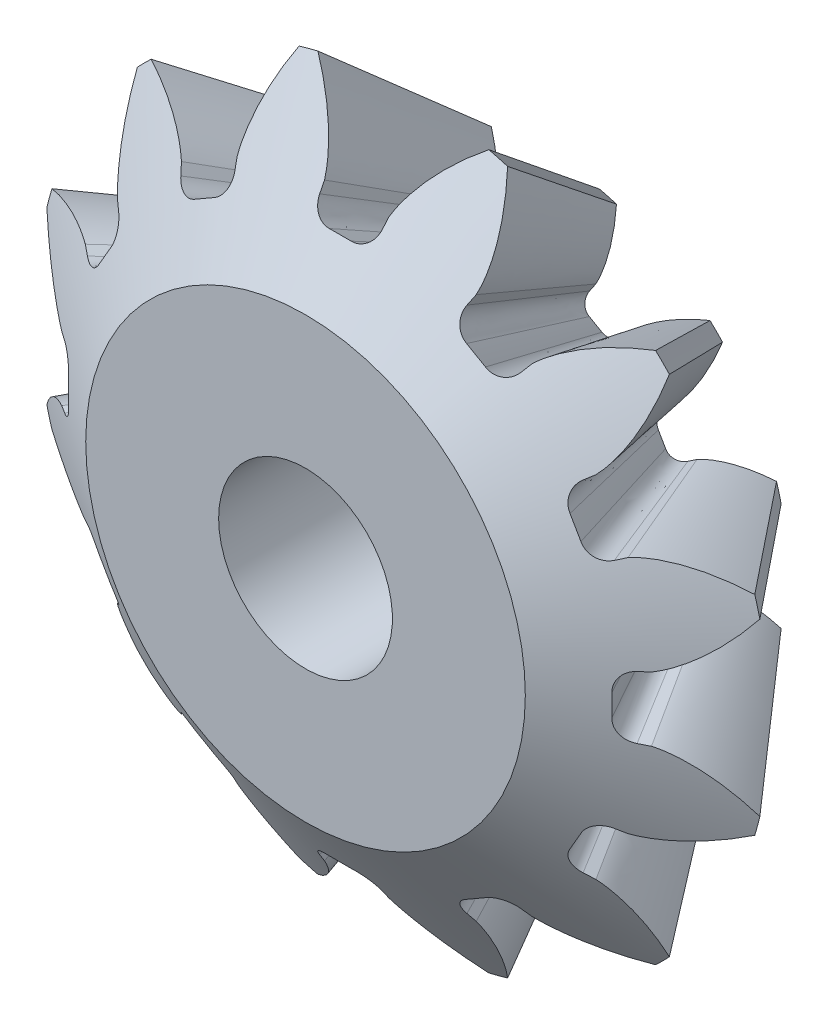
SolidWorks part; units mm, degrees
ref_plane "Front Plane" through (0, 0, 0) normal (0, 0, 1) x (1, 0, 0)
ref_plane "Top Plane" through (0, 0, 0) normal (0, 1, 0) x (1, 0, 0)
ref_plane "Right Plane" through (0, 0, 0) normal (1, 0, 0) x (0, 0, -1)
ref_axis "Gear Axis" through (0, 0, -1.3521) along (0, 0, 1)
sketch "Blank Sketch" plane through (0, 0, 0) normal (0, 1, 0) x (1, 0, 0)
  line L0 (0, 0) -> (0, -27.0416) construction
  line L1 (0, 0) -> (15, -22.5) construction
  line L2 (0, 0) -> (10.0077, -15.0115) construction
  line L3 (6.2136, -17.5409) -> (11.62, -13.9367)
  line L4 (11.62, -13.9367) -> (17.6117, -20.7589)
  line L5 (17.6117, -20.7589) -> (10.5604, -25.4597)
  line L6 (10.5604, -25.4597) -> (4.175, -25.4597)
  line L7 (4.175, -25.4597) -> (4.175, -17.5409)
  line L8 (4.175, -17.5409) -> (6.2136, -17.5409)
  line L9 (15, -22.5) -> (17.6117, -20.7589) construction
  line L10 (15, -22.5) -> (10.5604, -25.4597) construction
  line L11 (10.0077, -15.0115) -> (6.2136, -17.5409) construction
  dimension "Axis" = 27.0416
  dimension "Cone" = 33.69
  dimension "Heel" = 27.0416
  dimension "Toe Cone" = 33.69
  dimension "Toe" = 18.0416
  dimension "Heel Square" = 90
  dimension "Addendum" = 3.1389
  dimension "Root Square" = 90
  dimension "Heel Rim" = 5.3357
  dimension "Toe Square" = 90
  dimension "Toe Rim" = 4.5599
  dimension "Front Square" = 90
  dimension "Face" = 7.602
  dimension "Back" = 6.3854
  dimension "Front" = 2.0386
revolve "Blank" add sketch "Blank Sketch" angle 360 about L0
sketch "Cone Sketch" plane through (0, 0, 0) normal (0, 1, 0) x (1, 0, 0)
  line L0 (0, 0) -> (0, -27.0416) construction
  line L1 (0, 0) -> (16.3868, -24.5801)
  line L2 (0, 0) -> (8.6209, -12.9314)
  dimension "Axis" = 27.0416
  dimension "Toe Cone" = 33.69
  dimension "Heel Cone" = 33.69
  dimension "Heel" = 29.5416
  dimension "Toe" = 15.5416
ref_plane "Heel Plane" through (16.3868, 0, 24.5801) normal (0.5547, 0, 0.8321) x (0.8321, 0, -0.5547)
ref_plane "Toe Plane" through (8.6209, 0, 12.9314) normal (0.5547, 0, 0.8321) x (0.8321, 0, -0.5547)
sketch "Heel Section Sketch" plane through (16.3868, 0, 24.5801) normal (0.5547, 0, 0.8321) x (0.8321, 0, -0.5547)
  line L0 (0, 0) -> (-19.6944, 0) construction
  line L1 (-1.0664, 1.6899) -> (-1.6127, 1.6403)
  line L2 (-1.0664, -1.6899) -> (-1.6127, -1.6403)
  line L3 (5.066, 7.4419) -> (5.066, -7.4419)
  arc A0 (-1.6127, 1.6403) -> (-2.5562, 0.5721) centre (-1.5189, 0.6067) ccw
  arc A1 (-2.5562, -0.5721) -> (-1.6127, -1.6403) centre (-1.5189, -0.6067) ccw
  arc A2 (-2.5562, -0.5721) -> (-2.5562, 0.5721) centre (-19.6944, 0) ccw
  spline S0 degree 4 poles (-1.2286, 1.6567) (-1.181, 1.6651) (-1.0984, 1.6813) (-1.0131, 1.7021) (-0.8228, 1.7564) (-0.6581, 1.8142) (-0.4389, 1.8979) (-0.2207, 1.9951) (0.0234, 2.1136) (0.2563, 2.2395) (0.4886, 2.3742) (0.7144, 2.5158) (0.956, 2.6769) (1.2463, 2.8844) (1.5815, 3.1433) (1.9563, 3.4606) (2.3479, 3.8229) (2.7249, 4.2038) (3.0844, 4.5958) (3.432, 5.0072) (3.759, 5.4208) (4.0808, 5.8628) (4.3344, 6.231) (4.5664, 6.5952) (4.7511, 6.8911) (4.9903, 7.3038) (5.1238, 7.5431) (5.3385, 7.948) (5.41, 8.0942) (5.4674, 8.2082) knots 0 0 0 0 0 0.016753 0.031571 0.050064 0.068907 0.096646 0.124386 0.152126 0.179865 0.207605 0.235344 0.263084 0.300343 0.355823 0.411302 0.466781 0.52226 0.577739 0.633218 0.688697 0.744176 0.799656 0.827395 0.855135 0.910614 0.955307 1 1 1 1 1 construction
  spline S1 degree 4 poles (-1.0664, 1.6899) (-1.0354, 1.6973) (-0.9668, 1.7153) (-0.8228, 1.7564) (-0.6581, 1.8142) (-0.4389, 1.8979) (-0.2207, 1.9951) (0.0234, 2.1136) (0.2563, 2.2395) (0.4886, 2.3742) (0.7144, 2.5158) (0.956, 2.6769) (1.2463, 2.8844) (1.5815, 3.1433) (1.9563, 3.4606) (2.3479, 3.8229) (2.7249, 4.2038) (3.0844, 4.5958) (3.432, 5.0072) (3.759, 5.4208) (4.0808, 5.8628) (4.3344, 6.231) (4.5664, 6.5952) (4.7511, 6.8911) (4.9216, 7.1853) (5.0082, 7.3375) (5.066, 7.4419) knots 0.016753 0.016753 0.016753 0.016753 0.016753 0.031571 0.050064 0.068907 0.096646 0.124386 0.152126 0.179865 0.207605 0.235344 0.263084 0.300343 0.355823 0.411302 0.466781 0.52226 0.577739 0.633218 0.688697 0.744176 0.799656 0.827395 0.855135 0.910614 0.910614 0.910614 0.910614 0.910614
  spline S2 degree 4 poles (-1.2286, -1.6567) (-1.181, -1.6651) (-1.0984, -1.6813) (-1.0131, -1.7021) (-0.8228, -1.7564) (-0.6581, -1.8142) (-0.4389, -1.8979) (-0.2207, -1.9951) (0.0234, -2.1136) (0.2563, -2.2395) (0.4886, -2.3742) (0.7144, -2.5158) (0.956, -2.6769) (1.2463, -2.8844) (1.5815, -3.1433) (1.9563, -3.4606) (2.3479, -3.8229) (2.7249, -4.2038) (3.0844, -4.5958) (3.432, -5.0072) (3.759, -5.4208) (4.0808, -5.8628) (4.3344, -6.231) (4.5664, -6.5952) (4.7511, -6.8911) (4.9903, -7.3038) (5.1238, -7.5431) (5.3385, -7.948) (5.41, -8.0942) (5.4674, -8.2082) knots 0 0 0 0 0 0.016753 0.031571 0.050064 0.068907 0.096646 0.124386 0.152126 0.179865 0.207605 0.235344 0.263084 0.300343 0.355823 0.411302 0.466781 0.52226 0.577739 0.633218 0.688697 0.744176 0.799656 0.827395 0.855135 0.910614 0.955307 1 1 1 1 1 construction
  spline S3 degree 4 poles (-1.0664, -1.6899) (-1.0354, -1.6973) (-0.9668, -1.7153) (-0.8228, -1.7564) (-0.6581, -1.8142) (-0.4389, -1.8979) (-0.2207, -1.9951) (0.0234, -2.1136) (0.2563, -2.2395) (0.4886, -2.3742) (0.7144, -2.5158) (0.956, -2.6769) (1.2463, -2.8844) (1.5815, -3.1433) (1.9563, -3.4606) (2.3479, -3.8229) (2.7249, -4.2038) (3.0844, -4.5958) (3.432, -5.0072) (3.759, -5.4208) (4.0808, -5.8628) (4.3344, -6.231) (4.5664, -6.5952) (4.7511, -6.8911) (4.9216, -7.1853) (5.0082, -7.3375) (5.066, -7.4419) knots 0.016753 0.016753 0.016753 0.016753 0.016753 0.031571 0.050064 0.068907 0.096646 0.124386 0.152126 0.179865 0.207605 0.235344 0.263084 0.300343 0.355823 0.411302 0.466781 0.52226 0.577739 0.633218 0.688697 0.744176 0.799656 0.827395 0.855135 0.910614 0.910614 0.910614 0.910614 0.910614
  dimension "Root" = 17.1478
  dimension "Fillet" = 1.0378
  dimension "Centre" = 19.6944
sketch "Toe Section Sketch" plane through (8.6209, 0, 12.9314) normal (0.5547, 0, 0.8321) x (0.8321, 0, -0.5547)
  line L0 (0, 0) -> (-10.3611, 0) construction
  line L1 (-0.561, 0.889) -> (-0.8484, 0.863)
  line L2 (-0.561, -0.889) -> (-0.8484, -0.863)
  line L3 (2.6652, 3.9151) -> (2.6652, -3.9151)
  arc A0 (-0.8484, 0.863) -> (-1.3448, 0.301) centre (-0.7991, 0.3192) ccw
  arc A1 (-1.3448, -0.301) -> (-0.8484, -0.863) centre (-0.7991, -0.3192) ccw
  arc A2 (-1.3448, -0.301) -> (-1.3448, 0.301) centre (-10.3611, 0) ccw
  spline S0 degree 4 poles (-0.6464, 0.8716) (-0.6213, 0.876) (-0.5778, 0.8845) (-0.533, 0.8955) (-0.4329, 0.924) (-0.3462, 0.9544) (-0.2309, 0.9985) (-0.1161, 1.0496) (0.0123, 1.112) (0.1348, 1.1782) (0.2571, 1.2491) (0.3758, 1.3235) (0.503, 1.4084) (0.6555, 1.5172) (0.8323, 1.6541) (1.0288, 1.8199) (1.2358, 2.0122) (1.4327, 2.21) (1.6242, 2.4204) (1.8032, 2.6299) (1.9816, 2.859) (2.1402, 3.0723) (2.311, 3.3268) (2.4415, 3.5271) (2.6102, 3.8151) (2.6985, 3.9736) (2.8046, 4.1741) (2.849, 4.2635) (2.8753, 4.3163) knots 0 0 0 0 0 0.016753 0.031571 0.050064 0.068907 0.096646 0.124386 0.152126 0.179865 0.207605 0.235344 0.263084 0.300343 0.355823 0.411302 0.466781 0.52226 0.577739 0.633218 0.688697 0.744176 0.799656 0.855135 0.910614 0.955307 1 1 1 1 1 construction
  spline S1 degree 4 poles (-0.561, 0.889) (-0.5447, 0.893) (-0.5086, 0.9024) (-0.4329, 0.924) (-0.3462, 0.9544) (-0.2309, 0.9985) (-0.1161, 1.0496) (0.0123, 1.112) (0.1348, 1.1782) (0.2571, 1.2491) (0.3758, 1.3235) (0.503, 1.4084) (0.6555, 1.5172) (0.8323, 1.6541) (1.0288, 1.8199) (1.2358, 2.0122) (1.4327, 2.21) (1.6242, 2.4204) (1.8032, 2.6299) (1.9816, 2.859) (2.1402, 3.0723) (2.311, 3.3268) (2.4415, 3.5271) (2.5745, 3.7541) (2.6348, 3.8602) (2.6652, 3.9151) knots 0.016753 0.016753 0.016753 0.016753 0.016753 0.031571 0.050064 0.068907 0.096646 0.124386 0.152126 0.179865 0.207605 0.235344 0.263084 0.300343 0.355823 0.411302 0.466781 0.52226 0.577739 0.633218 0.688697 0.744176 0.799656 0.855135 0.910614 0.910614 0.910614 0.910614 0.910614
  spline S2 degree 4 poles (-0.6464, -0.8716) (-0.6213, -0.876) (-0.5778, -0.8845) (-0.533, -0.8955) (-0.4329, -0.924) (-0.3462, -0.9544) (-0.2309, -0.9985) (-0.1161, -1.0496) (0.0123, -1.112) (0.1348, -1.1782) (0.2571, -1.2491) (0.3758, -1.3235) (0.503, -1.4084) (0.6555, -1.5172) (0.8323, -1.6541) (1.0288, -1.8199) (1.2358, -2.0122) (1.4327, -2.21) (1.6242, -2.4204) (1.8032, -2.6299) (1.9816, -2.859) (2.1402, -3.0723) (2.311, -3.3268) (2.4415, -3.5271) (2.6102, -3.8151) (2.6985, -3.9736) (2.8046, -4.1741) (2.849, -4.2635) (2.8753, -4.3163) knots 0 0 0 0 0 0.016753 0.031571 0.050064 0.068907 0.096646 0.124386 0.152126 0.179865 0.207605 0.235344 0.263084 0.300343 0.355823 0.411302 0.466781 0.52226 0.577739 0.633218 0.688697 0.744176 0.799656 0.855135 0.910614 0.955307 1 1 1 1 1 construction
  spline S3 degree 4 poles (-0.561, -0.889) (-0.5447, -0.893) (-0.5086, -0.9024) (-0.4329, -0.924) (-0.3462, -0.9544) (-0.2309, -0.9985) (-0.1161, -1.0496) (0.0123, -1.112) (0.1348, -1.1782) (0.2571, -1.2491) (0.3758, -1.3235) (0.503, -1.4084) (0.6555, -1.5172) (0.8323, -1.6541) (1.0288, -1.8199) (1.2358, -2.0122) (1.4327, -2.21) (1.6242, -2.4204) (1.8032, -2.6299) (1.9816, -2.859) (2.1402, -3.0723) (2.311, -3.3268) (2.4415, -3.5271) (2.5745, -3.7541) (2.6348, -3.8602) (2.6652, -3.9151) knots 0.016753 0.016753 0.016753 0.016753 0.016753 0.031571 0.050064 0.068907 0.096646 0.124386 0.152126 0.179865 0.207605 0.235344 0.263084 0.300343 0.355823 0.411302 0.466781 0.52226 0.577739 0.633218 0.688697 0.744176 0.799656 0.855135 0.910614 0.910614 0.910614 0.910614 0.910614
  dimension "Root" = 9.0213
  dimension "Fillet" = 0.546
  dimension "Centre" = 10.3611
loft "Tooth Space" cut profiles "Heel Section Sketch", "Toe Section Sketch"
pattern_circular "Teeth" count 12 over 360 about axis through (0, 0, -1.3521) along (0, 0, 1) of "Tooth Space"
equation "\"No. of Teeth\"= 12"
equation "\"Module\"= 2.5"
equation "\"Bore Diameter\"= 8.35"
equation "\"Pressure Angle\"= 20"
equation "\"Shaft Angle\"= 90"
equation "\"Mate Teeth\"= 18"
equation "\"Pitch Cone Angle\"= IIF ( ( \"Mate Teeth\" / \"No. of Teeth\" + cos ( \"Shaft Angle\" ) ) > 0 , atn ( sin ( \"Shaft Angle\" ) / ( \"Mate Teeth\" / \"No. of Teeth\" + cos ( \"Shaft Angle\" ) ) ) , 180 + atn ( sin ( \"Shaft Angle\" ) / ( \"Mate Teeth\" / \"No. of Teeth\" + cos ( \"Shaft Angle\" ) ) ) )"
equation "\"Mate Cone Angle\"= \"Shaft Angle\" - \"Pitch Cone Angle\""
equation "\"Addendum\"= IIF ( \"No. of Teeth\" >= \"Mate Teeth\" , 0.54 * \"Module\" + 0.46 * \"Module\" / ( ( \"No. of Teeth\" * cos ( \"Mate Cone Angle\" ) ) / ( \"Mate Teeth\" * cos ( \"Pitch Cone Angle\" ) ) ) , 2 * \"Module\" - ( 0.54 * \"Module\" + 0.46 * \"Module\" / ( ( \"Mate Teeth\" * cos ( \"Pitch Cone Angle\" ) ) / ( \"No. of Teeth\" * cos ( \"Mate Cone Angle\" ) ) ) ) )"
equation "\"Outer Diameter\"= \"No. of Teeth\" * \"Module\" + 2 * \"Addendum\" * cos ( \"Pitch Cone Angle\" )"
equation "\"Pitch Diameter\"= \"No. of Teeth\" * \"Module\""
equation "\"Backlash\"= IIF ( \"Module\" <= 1 , 0.3 * \"Module\" , 0.3 )"
equation "\"Arc Length\"= ( ( \"Module\" * pi ) / 2 + \"Backlash\" - 2 * ( \"Addendum\" - \"Module\" ) * tan ( \"Pressure Angle\" ) )"
equation "\"Fillet Radius\"= 0.38 * \"Module\""
equation "\"Mate Addendum\"= 2 * \"Module\" - \"Addendum\""
equation "\"Dedendum\"= 2.188 * \"Module\" - \"Addendum\""
equation "\"Tooth Depth\"= \"Addendum\" + \"Dedendum\""
equation "\"Mate Dedendum\"= 2.188 * \"Module\" - \"Mate Addendum\""
equation "\"Face Width\"= 9"
equation "\"Cone Distance\"= \"Pitch Diameter\" / ( 2 * sin ( \"Pitch Cone Angle\" ) )"
equation "\"Dedendum Angle\"= atn ( \"Dedendum\" / \"Cone Distance\" )"
equation "\"Mate Dedendum Angle\"= atn ( \"Mate Dedendum\" / \"Cone Distance\" )"
equation "\"Face Angle\"= \"Pitch Cone Angle\" + \"Mate Dedendum Angle\""
equation "\"Root Angle\"= \"Pitch Cone Angle\" - \"Dedendum Angle\""
equation "\"Overrun\"= \"Module\""
equation "\"Back Cone Pitch Diameter\"= \"Pitch Diameter\" / cos ( \"Pitch Cone Angle\" )"
equation "\"Back Cone Outer Diameter\"= \"Back Cone Pitch Diameter\" + 2 * \"Addendum\""
equation "\"Root Diameter\"= \"Back Cone Outer Diameter\" - 2 * \"Tooth Depth\""
equation "\"Base Diameter\"= \"Back Cone Pitch Diameter\" * cos ( \"Pressure Angle\" )"
equation "\"Base Radius\"= \"Base Diameter\" / 2"
equation "\"Tooth Thickness\"= \"Module\" * pi - \"Arc Length\""
equation "\"Half Space Angle\"= ( \"Arc Length\" / \"Back Cone Pitch Diameter\" ) * 180 / pi"
equation "\"Involute Fn\"= tan ( \"Pressure Angle\" ) - \"Pressure Angle\" * pi / 180"
equation "\"Flank Offset\"= \"Arc Length\" / \"Back Cone Pitch Diameter\" - \"Involute Fn\""
equation "\"Tip Cap Diameter\"= \"Back Cone Outer Diameter\" + 2 * \"Module\""
equation "\"Flank Start Diameter\"= IIF ( \"Base Diameter\" >= ( \"Root Diameter\" + 3 * \"Fillet Radius\" ) , \"Base Diameter\" , \"Root Diameter\" + 3 * \"Fillet Radius\" )"
equation "\"Involute t1\"= ( abs ( ( \"Flank Start Diameter\" / \"Base Diameter\" ) ^ 2 - 1 ) ) ^ 0.5"
equation "\"Involute t2\"= ( abs ( ( \"Tip Cap Diameter\" / \"Base Diameter\" ) ^ 2 - 1 ) ) ^ 0.5"
equation "\"Flank Arc Radius\"= ( \"Back Cone Pitch Diameter\" / 2 ) * sin ( \"Pressure Angle\" )"
equation "\"Flank Centre Angle\"= \"Half Space Angle\" + \"Pressure Angle\""
equation "\"Heel Distance\"= \"Cone Distance\" + \"Overrun\""
equation "\"Toe Distance\"= \"Cone Distance\" - \"Face Width\" - \"Overrun\""
equation "\"Heel Scale\"= \"Heel Distance\" / \"Cone Distance\""
equation "\"Toe Scale\"= \"Toe Distance\" / \"Cone Distance\""
equation "\"Heel Virtual Radius\"= \"Heel Distance\" * tan ( \"Pitch Cone Angle\" )"
equation "\"Toe Virtual Radius\"= \"Toe Distance\" * tan ( \"Pitch Cone Angle\" )"
equation "\"Axis@Blank Sketch\"= \"Cone Distance\""
equation "\"Cone@Blank Sketch\"= \"Pitch Cone Angle\""
equation "\"Heel@Blank Sketch\"= \"Cone Distance\""
equation "\"Toe Cone@Blank Sketch\"= \"Pitch Cone Angle\""
equation "\"Toe@Blank Sketch\"= \"Cone Distance\" - \"Face Width\""
equation "\"Addendum@Blank Sketch\"= \"Addendum\""
equation "\"Heel Rim@Blank Sketch\"= \"Dedendum\" + \"Module\" / cos ( \"Pitch Cone Angle\" )"
equation "\"Toe Rim@Blank Sketch\"= \"Dedendum\" - \"Face Width\" * tan ( \"Dedendum Angle\" ) + \"Module\" / cos ( \"Pitch Cone Angle\" )"
equation "\"Face@Blank Sketch\"= \"Mate Dedendum Angle\""
equation "\"Back@Blank Sketch\"= \"Cone Distance\" * sin ( \"Pitch Cone Angle\" ) - \"Dedendum\" * cos ( \"Pitch Cone Angle\" ) - \"Module\" - \"Bore Diameter\" / 2"
equation "\"Front@Blank Sketch\"= ( \"Cone Distance\" - \"Face Width\" ) * sin ( \"Pitch Cone Angle\" ) - ( \"Dedendum\" - \"Face Width\" * tan ( \"Dedendum Angle\" ) + \"Module\" / cos ( \"Pitch Cone Angle\" ) ) * cos ( \"Pitch Cone Angle\" ) - \"Bore Diameter\" / 2"
equation "\"Axis@Cone Sketch\"= \"Cone Distance\""
equation "\"Heel Cone@Cone Sketch\"= \"Pitch Cone Angle\""
equation "\"Heel@Cone Sketch\"= \"Heel Distance\""
equation "\"Toe Cone@Cone Sketch\"= \"Pitch Cone Angle\""
equation "\"Toe@Cone Sketch\"= \"Toe Distance\""
equation "\"Centre@Heel Section Sketch\"= \"Heel Virtual Radius\""
equation "\"Root@Heel Section Sketch\"= ( \"Root Diameter\" / 2 ) * \"Heel Scale\""
equation "\"Fillet@Heel Section Sketch\"= ( \"Fillet Radius\" ) * \"Heel Scale\""
equation "\"Centre@Toe Section Sketch\"= \"Toe Virtual Radius\""
equation "\"Root@Toe Section Sketch\"= ( \"Root Diameter\" / 2 ) * \"Toe Scale\""
equation "\"Fillet@Toe Section Sketch\"= ( \"Fillet Radius\" ) * \"Toe Scale\""
equation "\"Count@Teeth\"= \"No. of Teeth\""
